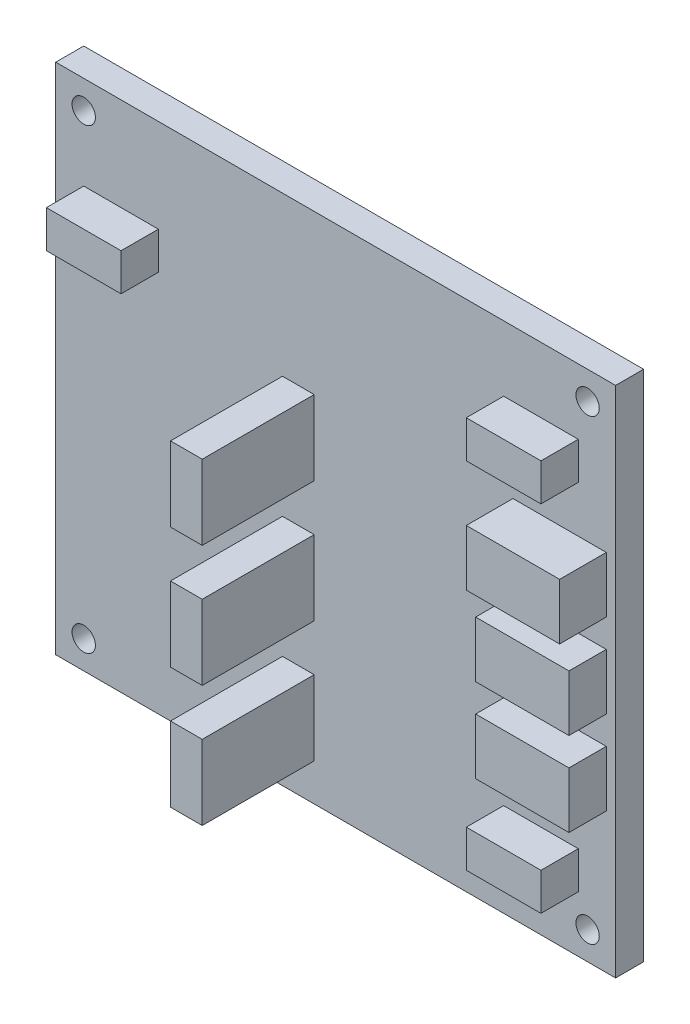
SolidWorks part; units mm, degrees
ref_plane "Front Plane" through (0, 0, 0) normal (0, 0, 1) x (1, 0, 0)
ref_plane "Top Plane" through (0, 0, 0) normal (0, 1, 0) x (1, 0, 0)
ref_plane "Right Plane" through (0, 0, 0) normal (1, 0, 0) x (0, 0, -1)
sketch "Sketch1" plane through (0, 0, 0) normal (0, 0, 1) x (1, 0, 0)
  line L1 (0, 0) -> (76.2, 0)
  line L2 (0, 0) -> (0, 69.85)
  line L3 (0, 69.85) -> (76.2, 69.85)
  line L4 (76.2, 0) -> (76.2, 69.85)
  dimension "D1" = 69.85
  dimension "D2" = 76.2
extrude "Boss-Extrude1" add sketch "Sketch1" along normal blind 3.81
sketch "Sketch2" plane through (0, 0, 3.81) normal (0, 0, 1) x (1, 0, 0)
  line L0 (76.2, 69.85) -> (0, 69.85) construction
  line L1 (0, 69.85) -> (0, 0) construction
  line L2 (76.2, 0) -> (76.2, 69.85) construction
  line L3 (0, 0) -> (76.2, 0) construction
  circle A0 centre (3.81, 66.04) radius 1.5875
  circle A1 centre (72.39, 66.04) radius 1.5875
  circle A2 centre (72.39, 3.81) radius 1.5875
  circle A3 centre (3.81, 3.81) radius 1.5875
  dimension "D3" = 3.175
  dimension "D6" = 3.175
  dimension "D7" = 3.81
  dimension "D9" = 3.175
  dimension "D12" = 3.175
  dimension "D1" = 3.81
  dimension "D2" = 3.81
  dimension "D4" = 3.81
  dimension "D5" = 3.81
  dimension "D8" = 3.81
  dimension "D10" = 3.81
  dimension "D11" = 3.81
extrude "Cut-Extrude1" cut sketch "Sketch2" against normal through all
sketch "Sketch3" plane through (0, 0, 3.81) normal (0, 0, 1) x (1, 0, 0)
  line L0 (0, 0) -> (76.2, 0) construction
  line L1 (3.81, 57.15) -> (13.97, 57.15)
  line L2 (3.81, 57.15) -> (3.81, 52.07)
  line L3 (3.81, 52.07) -> (13.97, 52.07)
  line L4 (13.97, 57.15) -> (13.97, 52.07)
  line L5 (3.81, 57.15) -> (13.97, 52.07) construction
  line L6 (3.81, 52.07) -> (13.97, 57.15) construction
  line L7 (0, 69.85) -> (0, 0) construction
  line L9 (60.96, 60.96) -> (71.12, 60.96)
  line L10 (60.96, 60.96) -> (60.96, 55.88)
  line L11 (60.96, 55.88) -> (71.12, 55.88)
  line L12 (71.12, 60.96) -> (71.12, 55.88)
  line L13 (60.96, 60.96) -> (71.12, 55.88) construction
  line L14 (60.96, 55.88) -> (71.12, 60.96) construction
  line L15 (62.23, 49.53) -> (74.93, 49.53)
  line L16 (62.23, 49.53) -> (62.23, 41.91)
  line L17 (62.23, 41.91) -> (74.93, 41.91)
  line L18 (74.93, 49.53) -> (74.93, 41.91)
  line L19 (62.23, 49.53) -> (74.93, 41.91) construction
  line L20 (62.23, 41.91) -> (74.93, 49.53) construction
  line L23 (62.23, 38.1) -> (74.93, 38.1)
  line L24 (62.23, 38.1) -> (62.23, 30.48)
  line L25 (62.23, 30.48) -> (74.93, 30.48)
  line L26 (74.93, 38.1) -> (74.93, 30.48)
  line L27 (62.23, 38.1) -> (74.93, 30.48) construction
  line L28 (62.23, 30.48) -> (74.93, 38.1) construction
  line L29 (62.23, 19.05) -> (74.93, 19.05)
  line L30 (62.23, 19.05) -> (62.23, 26.67)
  line L31 (62.23, 26.67) -> (74.93, 26.67)
  line L32 (74.93, 19.05) -> (74.93, 26.67)
  line L33 (62.23, 19.05) -> (74.93, 26.67) construction
  line L34 (62.23, 26.67) -> (74.93, 19.05) construction
  line L35 (60.96, 12.7) -> (71.12, 12.7)
  line L36 (60.96, 12.7) -> (60.96, 7.62)
  line L37 (60.96, 7.62) -> (71.12, 7.62)
  line L38 (71.12, 12.7) -> (71.12, 7.62)
  line L39 (60.96, 12.7) -> (71.12, 7.62) construction
  line L40 (60.96, 7.62) -> (71.12, 12.7) construction
  point P0 (8.89, 54.61)
  point P9 (66.04, 58.42)
  point P14 (68.58, 45.72)
  point P19 (68.58, 34.29)
  point P24 (68.58, 22.86)
  point P29 (66.04, 10.16)
  dimension "D1" = 54.61
  dimension "D2" = 8.89
  dimension "D3" = 5.08
  dimension "D4" = 10.16
  dimension "D5" = 58.42
  dimension "D6" = 66.04
  dimension "D7" = 10.16
  dimension "D8" = 5.08
  dimension "D9" = 68.58
  dimension "D10" = 45.72
  dimension "D11" = 7.62
  dimension "D12" = 12.7
  dimension "D13" = 68.58
  dimension "D14" = 34.29
  dimension "D15" = 12.7
  dimension "D16" = 7.62
  dimension "D17" = 68.58
  dimension "D18" = 22.86
  dimension "D19" = 12.7
  dimension "D20" = 7.62
  dimension "D21" = 66.04
  dimension "D22" = 10.16
  dimension "D23" = 10.16
  dimension "D24" = 5.08
extrude "Boss-Extrude2" add sketch "Sketch3" along normal blind 6.35 contours L15 L18 L17 L16
extrude "Boss-Extrude3" add sketch "Sketch3<4>" along normal blind 5.08
sketch "Sketch3<4>" plane through (0, 0, 3.81) normal (0, 0, 1) x (1, 0, 0) same geometry as "Sketch3"
sketch "Sketch6" plane through (0, 0, 3.81) normal (0, 0, 1) x (1, 0, 0)
  line L0 (0, 69.85) -> (0, 0) construction
  line L1 (30.861, 48.26) -> (35.179, 48.26)
  line L2 (30.861, 48.26) -> (30.861, 38.1)
  line L3 (30.861, 38.1) -> (35.179, 38.1)
  line L4 (35.179, 48.26) -> (35.179, 38.1)
  line L5 (30.861, 48.26) -> (35.179, 38.1) construction
  line L6 (30.861, 38.1) -> (35.179, 48.26) construction
  line L7 (0, 0) -> (76.2, 0) construction
  line L9 (30.861, 31.75) -> (35.179, 31.75)
  line L10 (30.861, 31.75) -> (30.861, 21.59)
  line L11 (30.861, 21.59) -> (35.179, 21.59)
  line L12 (35.179, 31.75) -> (35.179, 21.59)
  line L13 (30.861, 31.75) -> (35.179, 21.59) construction
  line L14 (30.861, 21.59) -> (35.179, 31.75) construction
  line L15 (30.861, 15.24) -> (35.179, 15.24)
  line L16 (30.861, 15.24) -> (30.861, 5.08)
  line L17 (30.861, 5.08) -> (35.179, 5.08)
  line L18 (35.179, 15.24) -> (35.179, 5.08)
  line L19 (30.861, 15.24) -> (35.179, 5.08) construction
  line L20 (30.861, 5.08) -> (35.179, 15.24) construction
  point P0 (33.02, 43.18)
  point P9 (33.02, 26.67)
  point P14 (33.02, 10.16)
  dimension "D1" = 33.02
  dimension "D2" = 43.18
  dimension "D3" = 4.318
  dimension "D4" = 10.16
  dimension "D5" = 33.02
  dimension "D6" = 26.67
  dimension "D7" = 33.02
  dimension "D8" = 10.16
  dimension "D9" = 10.16
  dimension "D10" = 4.318
  dimension "D11" = 4.318
  dimension "D12" = 10.16
extrude "Boss-Extrude4" add sketch "Sketch6" along normal blind 15.24
